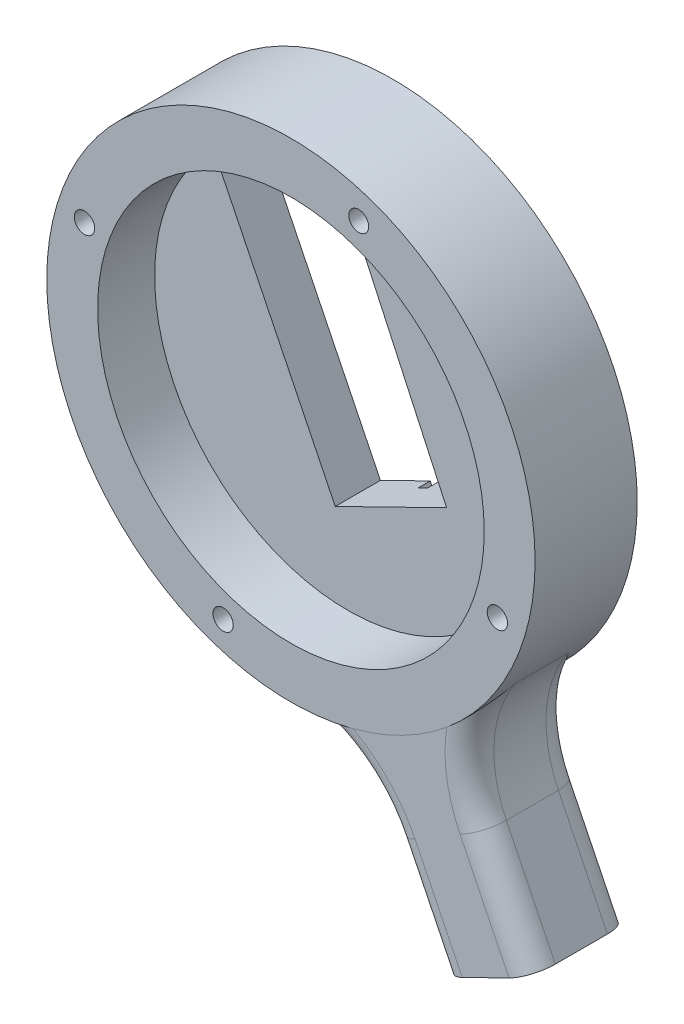
SolidWorks part; units mm, degrees
ref_plane "Front Plane" through (0, 0, 0) normal (0, 0, 1) x (1, 0, 0)
ref_plane "Top Plane" through (0, 0, 0) normal (0, 1, 0) x (1, 0, 0)
ref_plane "Right Plane" through (0, 0, 0) normal (1, 0, 0) x (0, 0, -1)
sketch "Sketch1" plane through (0, 0, 0) normal (0, 0, 1) x (1, 0, 0)
  circle A0 centre (0, 0) radius 60
  dimension "D1" = 120
extrude "Boss-Extrude1" add sketch "Sketch1" along normal blind 25.1
sketch "Sketch2" plane through (0, 0, 25.1) normal (0, 0, 1) x (1, 0, 0)
  circle A0 centre (-16.6647, -50.7331) radius 2.495
  circle A1 centre (-50.7331, 16.6647) radius 2.5
  circle A2 centre (16.6647, 50.7331) radius 2.4444
  circle A3 centre (50.7331, -16.6647) radius 2.5
sketch "Sketch3" plane through (0, 0, 25.1) normal (0, 0, 1) x (1, 0, 0)
  circle A0 centre (0, 0) radius 47.5
  dimension "D1" = 95
extrude "Cut-Extrude2" cut sketch "Sketch3" against normal blind 14
extrude "Cut-Extrude5" cut sketch "Sketch2" against normal through all both and the other way through all
sketch "Sketch6" plane through (0, 0, 0) normal (0, 0, -1) x (-1, 0, 0)
  circle A0 centre (11.9735, 47.2126) radius 3
  circle A1 centre (27.3813, 40.0293) radius 3
  circle A2 centre (-19.7177, -20.7629) radius 3
  circle A3 centre (-4.3099, -27.9462) radius 3
  dimension "D1" = 6
  dimension "D2" = 6
  dimension "D3" = 6
  dimension "D4" = 6
extrude "Cut-Extrude6" cut sketch "Sketch6" against normal blind 6
sketch "Sketch7" plane through (0, 0, 11.1) normal (0, 0, 1) x (1, 0, 0)
  line L0 (-32.4009, 32.8719) -> (-3.109, -26.9124)
  line L1 (-3.109, -26.9124) -> (24.2542, -13.5055)
  line L2 (24.2542, -13.5055) -> (-3.6508, 46.9583)
  line L3 (-3.6508, 46.9583) -> (-32.4009, 32.8719)
  circle A0 centre (0, 0) radius 47.1 construction
extrude "Cut-Extrude7" cut sketch "Sketch7" against normal through all both and the other way through all
ref_plane "Plane1" through (33.538, -68.4503, 0) normal (0.44, -0.898, 0) x (-0.898, -0.44, 0)
sketch "Sketch8" plane through (33.538, -68.4503, 0) normal (0.44, -0.898, 0) x (-0.898, -0.44, 0)
  line L1 (-13.3812, -0.0782) -> (11.4188, -0.0782)
  line L2 (-13.3812, -0.0782) -> (-13.3812, -24.8782)
  line L3 (-13.3812, -24.8782) -> (11.4188, -24.8782)
  line L4 (11.4188, -0.0782) -> (11.4188, -24.8782)
  line L5 (-13.3812, -0.0782) -> (11.4188, -24.8782) construction
  line L6 (-13.3812, -24.8782) -> (11.4188, -0.0782) construction
  point P0 (-0.9812, -12.4782)
  dimension "D1" = 24.8
  dimension "D2" = 24.8
extrude "Boss-Extrude2" add sketch "Sketch8" along normal blind 30 and the other way blind 23
fillet "Fillet1" radius 30 2 edges at (15.6626, -57.9196, 12.4782) (37.7507, -46.6357, 12.4782)
sketch "Sketch9" plane through (46.7376, -95.3905, 0) normal (0.44, -0.898, 0) x (0.898, 0.44, 0)
  circle A0 centre (0.9812, 12.4782) radius 6.1
  dimension "D1" = 12.2
extrude "Cut-Extrude8" cut sketch "Sketch9" against normal blind 40
fillet "Fillet2" radius 6 8 edges at (14.1239, -64.7026, 0.0782) (43.7436, -49.377, 0.0782) (43.7436, -49.377, 24.8782) (14.1239, -64.7026, 24.8782) (30.6928, -88.596, 0.0782) (52.7327, -77.2136, 0.0782) (52.7327, -77.2136, 24.8782) (30.6928, -88.596, 24.8782)
sketch "Sketch12" plane through (0, 0, 0) normal (0, 0, -1) x (-1, 0, 0)
  line L0 (16.5698, 40.6285) -> (19.584, 46.7804)
  line L1 (3.6508, 46.9583) -> (32.4009, 32.8719) construction
  line L2 (19.584, 46.7804) -> (22.1828, 45.5071)
  line L3 (22.1828, 45.5071) -> (19.1686, 39.3552)
  line L4 (19.1686, 39.3552) -> (16.5698, 40.6285)
  line L5 (-11.4581, -19.7751) -> (-14.3908, -26.3385)
  line L6 (3.109, -26.9124) -> (-24.2542, -13.5055) construction
  line L7 (-14.3908, -26.3385) -> (-12.0521, -27.3835)
  line L8 (-12.0521, -27.3835) -> (-9.1563, -20.9029)
  line L9 (-9.1563, -20.9029) -> (-11.4581, -19.7751)
extrude "Cut-Extrude9" cut sketch "Sketch12" against normal blind 3
